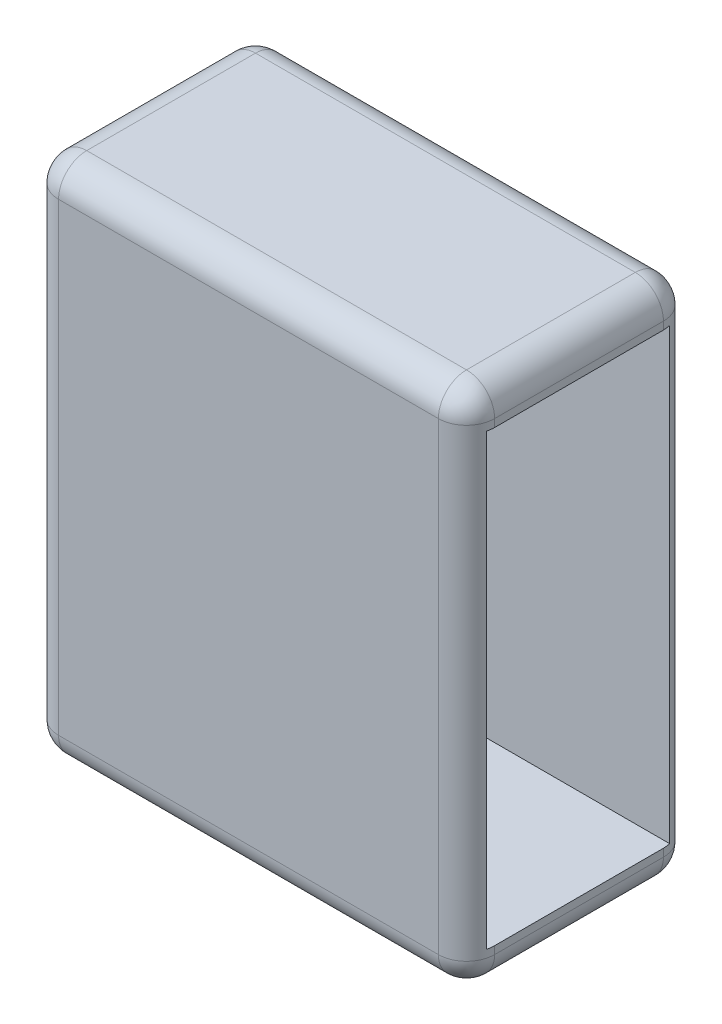
SolidWorks part; units mm, degrees
material "PLA"
ref_plane "Front Plane" through (0, 0, 0) normal (1, 0, 0) x (0, 1, 0)
ref_plane "Top Plane" through (0, 0, 0) normal (0, 0, 1) x (0, 1, 0)
ref_plane "Right Plane" through (0, 0, 0) normal (0, 1, 0) x (-1, 0, 0)
sketch "Sketch1" plane through (0, 0, 0) normal (1, 0, 0) x (0, 1, 0)
  line L5 (-37, 8) -> (-30.25, 8) construction
  line L6 (-37, 16) -> (0, 16)
  line L11 (-37, 16) -> (-37, 0)
  line L12 (-37, 0) -> (0, 0)
  line L20 (0, 16) -> (0, 0)
  line L21 (-30.25, 14.5) -> (-6.75, 14.5)
  line L22 (-30.25, 14.5) -> (-30.25, 1.5)
  line L23 (-30.25, 1.5) -> (-6.75, 1.5)
  line L24 (-6.75, 14.5) -> (-6.75, 1.5)
  line L25 (-6.75, 8) -> (0, 8) construction
  line L26 (-18.5, 0) -> (-18.5, 1.5) construction
  line L27 (-18.5, 16) -> (-18.5, 14.5) construction
  line L29 (-34.45, 1.5) -> (-2.55, 1.5)
  line L30 (-34.45, 1.5) -> (-34.45, 14.5)
  line L31 (-34.45, 14.5) -> (-2.55, 14.5)
  line L32 (-2.55, 1.5) -> (-2.55, 14.5)
  dimension "D1" = 4.2
  dimension "D2" = 13
  dimension "D3" = 4.2
  dimension "D6" = 37
  dimension "D7" = 23.5
  dimension "D9" = 1.5
extrude "Boss-Extrude1" add sketch "Sketch1" along normal blind 26 contours L20 L6 L11 L12 L21 L24 L23 L22 region at (0, -18.5, 15.5969)
extrude "Boss-Extrude2" add sketch "Sketch1<3>" along normal blind 2 contours L31 L30 L29 L22 | L29 L32 L31 L24 region at (0, -32.35, 8) region at (0, -4.65, 8)
sketch "Sketch1<3>" plane through (0, 0, 0) normal (1, 0, 0) x (0, 1, 0) same geometry as "Sketch1"
sketch "Sketch2" plane through (26, 0, 0) normal (1, 0, 0) x (0, 1, 0)
  line L1 (-37, 16) -> (0, 16)
  line L2 (-37, 16) -> (-37, 0)
  line L3 (-37, 0) -> (0, 0)
  line L4 (0, 16) -> (0, 0)
sketch "Sketch3" plane through (0, 0, 0) normal (-1, 0, 0) x (0, -1, 0)
  line L1 (0, 16) -> (37, 16)
  line L2 (0, 16) -> (0, 0)
  line L3 (0, 0) -> (37, 0)
  line L4 (37, 16) -> (37, 0)
  line L5 (2.55, 14.5) -> (34.45, 14.5)
  line L6 (2.55, 14.5) -> (2.55, 1.5)
  line L7 (2.55, 1.5) -> (34.45, 1.5)
  line L8 (34.45, 14.5) -> (34.45, 1.5)
extrude "Boss-Extrude4" add sketch "Sketch3" along normal blind 3.5
sketch "Sketch5" plane through (-3.5, 0, 0) normal (-1, 0, 0) x (0, -1, 0)
  line L0 (37, 8) -> (30.25, 8) construction
  line L1 (0, 16) -> (37, 16)
  line L2 (0, 16) -> (0, 0)
  line L3 (0, 0) -> (37, 0)
  line L4 (37, 16) -> (37, 0)
  line L5 (30.25, 14.5) -> (30.25, 1.5) construction
  circle A0 centre (23.25, 8) radius 5.2
  dimension "D1" = 10.4
  dimension "D2" = 7
extrude "Boss-Extrude5" add sketch "Sketch5" along normal blind 1.5
ref_plane "Plane1" through (26, 0, 16) normal (0, 0, -1) x (-1, 0, 0)
sketch "Sketch9" plane through (0, 0, 0) normal (0, 1, 0) x (-1, 0, 0)
  line L0 (-26, 8) -> (5, 8) construction
  line L3 (-26, 16) -> (-26, 0) construction
  line L4 (5, 16) -> (5, 0) construction
  line L5 (-2, 5.65) -> (-17, 4.4)
  line L6 (-2, 10.35) -> (-17, 11.6)
  circle A2 centre (-17, 8) radius 3.6
  circle A3 centre (-2, 8) radius 2.35
  circle A4 centre (-17, 8) radius 0.15
  circle A5 centre (-2, 8) radius 0.15
  dimension "D1" = 0.3
  dimension "D4" = 7.2
  dimension "D5" = 4.7
  dimension "D6" = 15
  dimension "D7" = 9
sketch "Sketch10" plane through (0, 0, 16) normal (0, 0, 1) x (1, 0, 0)
sketch "Sketch11" plane through (0, -37, 0) normal (0, -1, 0) x (1, 0, 0)
  line L0 (2.375, 8) -> (17.375, 8) construction
  line L1 (17.375, 4.4) -> (2.375, 5.65)
  line L2 (17.375, 11.6) -> (2.375, 10.35)
  line L3 (-5, 8) -> (0.025, 8) construction
  line L4 (-5, 0) -> (-5, 16) construction
  line L5 (20.975, 8) -> (26, 8) construction
  line L6 (26, 16) -> (26, 0) construction
  line L7 (2.375, 10.35) -> (2.375, 16) construction
  line L8 (26, 16) -> (-5, 16) construction
  line L9 (2.375, 0) -> (2.375, 5.65) construction
  line L10 (26, 0) -> (-5, 0) construction
  circle A0 centre (2.375, 8) radius 2.35
  circle A1 centre (17.375, 8) radius 3.6
  circle A2 centre (2.375, 8) radius 0.15
  circle A3 centre (17.375, 8) radius 0.15
  dimension "D1" = 4.7
  dimension "D2" = 7.2
  dimension "D4" = 0.3
  dimension "D3" = 15
extrude "Cut-Extrude5" cut sketch "Sketch11" against normal blind 1.5 contours A1 L2 A0 L1 | A1 A3 | L1 A0 L2 A2 | A3 | A2 region at (17.0855, -37, 4.5263) region at (9.5724, -37, 8) region at (0.0915, -37, 8) region at (2.375, -37, 8) region at (17.375, -37, 8)
extrude "Cut-Extrude12" cut sketch "Sketch11<7>" against normal blind 2 contours A2 | A3 region at (2.375, -37, 8) region at (17.375, -37, 8)
sketch "Sketch11<7>" plane through (0, -37, 0) normal (0, -1, 0) x (1, 0, 0) same geometry as "Sketch11"
fillet "Fillet1" radius 2 12 edges at (26, 0, 8) (26, -37, 8) (10.5, -37, 0) (-5, -37, 8) (-5, 0, 8) (-5, -18.5, 0) (10.5, 0, 0) (26, -18.5, 0) (26, -18.5, 16) (10.5, 0, 16) (-5, -18.5, 16) (10.5, -37, 16)
